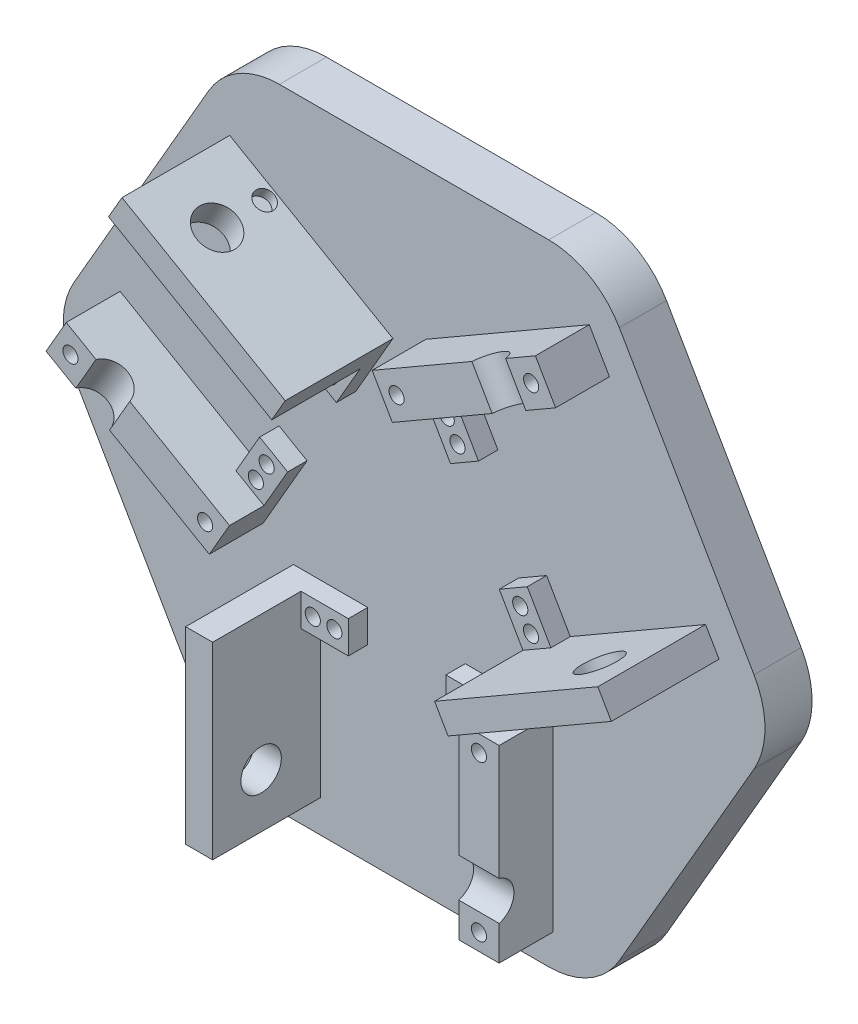
SolidWorks part; units mm, degrees
ref_plane "Front Plane" through (0, 0, 0) normal (0, 0, 1) x (1, 0, 0)
ref_plane "Top Plane" through (0, 0, 0) normal (0, 1, 0) x (1, 0, 0)
ref_plane "Right Plane" through (0, 0, 0) normal (1, 0, 0) x (0, 0, -1)
sketch "Sketch2" plane through (0, 0, 0) normal (0, 0, 1) x (1, 0, 0)
  line L1 (80.1682, 9.6234) -> (48.4182, 64.616)
  line L2 (31.75, 74.2394) -> (-31.75, 74.2394)
  line L3 (-48.4182, 64.616) -> (-80.1682, 9.6234)
  line L4 (-80.1682, -9.6234) -> (-48.4182, -64.616)
  line L5 (-31.75, -74.2394) -> (31.75, -74.2394)
  line L6 (48.4182, -64.616) -> (80.1682, -9.6234)
  circle A0 centre (0, 0) radius 74.2394 construction
  arc A1 (48.4182, 64.616) -> (31.75, 74.2394) centre (31.75, 54.9926) ccw
  arc A2 (80.1682, 9.6234) -> (80.1682, -9.6234) centre (63.5, 0) cw
  arc A3 (31.75, -74.2394) -> (48.4182, -64.616) centre (31.75, -54.9926) ccw
  arc A4 (-48.4182, -64.616) -> (-31.75, -74.2394) centre (-31.75, -54.9926) ccw
  arc A5 (-80.1682, 9.6234) -> (-80.1682, -9.6234) centre (-63.5, 0) ccw
  arc A6 (-31.75, 74.2394) -> (-48.4182, 64.616) centre (-31.75, 54.9926) ccw
  dimension "D1" = 63.5
extrude "Boss-Extrude1" add sketch "Sketch2" along normal blind 4.7625
sketch "Sketch4" plane through (0, 0, 4.7625) normal (0, 0, 1) x (1, 0, 0)
  line L0 (-31.75, -74.2394) -> (31.75, -74.2394) construction
  line L1 (-28.448, -66.6194) -> (-22.098, -66.6194)
  line L2 (-28.448, -66.6194) -> (-28.448, -22.1694)
  line L3 (-28.448, -22.1694) -> (-22.098, -22.1694)
  line L4 (-22.098, -66.6194) -> (-22.098, -22.1694)
  point P6 (0, -74.2394)
  point P17 (0, 0)
  dimension "D1" = 6.35
  dimension "D2" = 44.45
  dimension "D3" = 7.62
  dimension "D4" = 22.098
extrude "Boss-Extrude3" add sketch "Sketch4" along normal blind 25.4
sketch "Sketch5" plane through (0, 0, 4.7625) normal (0, 0, 1) x (1, 0, 0)
  line L1 (23.241, -66.6194) -> (32.766, -66.6194)
  line L2 (23.241, -66.6194) -> (23.241, -22.1694)
  line L3 (23.241, -22.1694) -> (32.766, -22.1694)
  line L4 (32.766, -66.6194) -> (32.766, -22.1694)
  line L6 (-28.448, -66.6194) -> (-22.098, -66.6194) construction
  line L7 (22.733, -61.8823) -> (22.733, -45.9565) construction
  line L8 (-22.098, -22.1694) -> (-28.448, -22.1694) construction
  point P12 (-66.5441, -10.5028)
  point P19 (0, 0)
  dimension "D1" = 9.525
  dimension "D2" = 0.508
extrude "Boss-Extrude6" add sketch "Sketch5" along normal blind 12.7
sketch "Sketch6" plane through (0, 0, 4.7625) normal (0, 0, 1) x (1, 0, 0)
  line L0 (12.065, -22.1694) -> (23.241, -22.1694)
  line L1 (-22.098, -22.1694) -> (-10.922, -22.1694)
  line L2 (-22.098, -22.1694) -> (-22.098, -29.7894)
  line L3 (-22.098, -29.7894) -> (-10.922, -29.7894)
  line L4 (-10.922, -22.1694) -> (-10.922, -29.7894)
  line L5 (12.065, -22.1694) -> (12.065, -29.7894)
  line L6 (12.065, -29.7894) -> (23.241, -29.7894)
  line L7 (23.241, -22.1694) -> (23.241, -29.7894)
  line L8 (23.241, -22.1694) -> (23.241, -66.6194) construction
  line L9 (32.766, -22.1694) -> (23.241, -22.1694) construction
  line L11 (-22.098, -66.6194) -> (-22.098, -22.1694) construction
  point P16 (0, 0)
  dimension "D1" = 7.62
  dimension "D2" = 11.176
  dimension "D3" = 7.62
  dimension "D4" = 11.176
extrude "Boss-Extrude5" add sketch "Sketch6" along normal blind 4.572
sketch "Sketch7" plane through (0, 0, 9.3345) normal (0, 0, 1) x (1, 0, 0)
  line L0 (-22.098, -29.7894) -> (-10.922, -29.7894) construction
  line L1 (-10.922, -29.7894) -> (-10.922, -22.1694) construction
  line L2 (12.065, -29.7894) -> (23.241, -29.7894) construction
  line L3 (12.065, -22.1694) -> (12.065, -29.7894) construction
  circle A0 centre (-19.304, -25.9794) radius 1.7907
  circle A1 centre (-14.224, -25.9794) radius 1.7907
  circle A2 centre (15.367, -25.9794) radius 1.7907
  circle A3 centre (20.447, -25.9794) radius 1.7907
  dimension "D1" = 3.5814
  dimension "D2" = 3.81
  dimension "D8" = 3.5814
  dimension "D9" = 3.5814
  dimension "D10" = 3.5814
  dimension "D3" = 5.08
  dimension "D4" = 3.302
  dimension "D5" = 3.81
  dimension "D6" = 3.302
  dimension "D7" = 5.08
extrude "Cut-Extrude1" cut sketch "Sketch7" against normal blind 6.731
sketch "Sketch9" plane through (-28.448, 0, 0) normal (-1, 0, 0) x (0, 0, 1)
  line L0 (4.7625, -22.1694) -> (4.7625, -66.6194) construction
  line L1 (30.1625, -66.6194) -> (4.7625, -66.6194) construction
  circle A0 centre (7.5311, -53.9194) radius 2.286
  dimension "D1" = 4.572
  dimension "D2" = 2.7686
  dimension "D3" = 12.7
sketch "Sketch10" plane through (-28.448, 0, 0) normal (-1, 0, 0) x (0, 0, 1)
  line L0 (30.1625, -66.6194) -> (4.7625, -66.6194) construction
  circle A0 centre (18.7325, -53.9194) radius 4.7625
  dimension "D1" = 9.525
  dimension "D2" = 11.2014
  dimension "D3" = 12.7
extrude "Cut-Extrude3" cut sketch "Sketch9" against normal blind 2.54
extrude "Cut-Extrude4" cut sketch "Sketch10" against normal up to surface (6.35 mm away) up to face at (-22.098, -39.5261, 14.7532)
sketch3d "3DSketch1"
  line L0 (0, 0, 0) -> (0, 0, 50000) construction
sketch "Sketch11" plane through (23.241, 0, 0) normal (-1, 0, 0) x (0, 0, 1)
  circle A0 centre (18.7325, -53.9194) radius 4.7625 construction
  circle A1 centre (18.7325, -53.9194) radius 4.7625 construction
  circle A2 centre (18.7325, -53.9194) radius 4.7625
  dimension "D1" = 9.525
extrude "Cut-Extrude5" cut sketch "Sketch11" against normal through all
sketch "Sketch12" plane through (0, 0, 17.4625) normal (0, 0, 1) x (1, 0, 0)
  line L0 (32.766, -49.3294) -> (32.766, -22.1694) construction
  line L2 (23.241, -66.6194) -> (32.766, -66.6194) construction
  line L3 (32.766, -22.1694) -> (23.241, -22.1694) construction
  circle A0 centre (28.0035, -26.0683) radius 1.778
  circle A1 centre (28.0035, -62.7205) radius 1.778
  dimension "D1" = 3.556
  dimension "D4" = 3.556
  dimension "D2" = 4.7625
  dimension "D3" = 3.8989
  dimension "D5" = 3.8989
extrude "Cut-Extrude6" cut sketch "Sketch12" against normal blind 6.731
pattern_circular "CirPattern1" count 3 over 360 about axis through (0, 0, 0) along (0, 0, 1) of "Boss-Extrude3", "Boss-Extrude6", "Boss-Extrude5", "Cut-Extrude1", "Cut-Extrude3", "Cut-Extrude4", "Cut-Extrude5", "Cut-Extrude6"
sketch "Sketch14" plane through (0, 0, 0) normal (0, 0, -1) x (-1, 0, 0)
  line L12 (-29.6639, 51.3794) -> (-59.3279, 0)
  line L13 (29.6639, 51.3794) -> (-29.6639, 51.3794)
  line L14 (59.3279, 0) -> (29.6639, 51.3794)
  line L15 (29.6639, -51.3794) -> (59.3279, 0)
  line L16 (-29.6639, -51.3794) -> (29.6639, -51.3794)
  line L17 (-59.3279, 0) -> (-29.6639, -51.3794)
  line L18 (-29.6639, 51.3794) -> (-59.3279, 0)
  line L19 (29.6639, 51.3794) -> (-29.6639, 51.3794)
  line L20 (59.3279, 0) -> (29.6639, 51.3794)
  line L21 (29.6639, -51.3794) -> (59.3279, 0)
  line L22 (-29.6639, -51.3794) -> (29.6639, -51.3794)
  line L23 (-59.3279, 0) -> (-29.6639, -51.3794)
  arc M7 (-31.75, 74.2394) -> (-48.4182, 64.616) centre (-31.75, 54.9926) ccw
  line M8 (-48.4182, 64.616) -> (-80.1682, 9.6234)
  arc M9 (-80.1682, 9.6234) -> (-80.1682, -9.6234) centre (-63.5, 0) ccw
  line M10 (-80.1682, -9.6234) -> (-48.4182, -64.616)
  arc M11 (-48.4182, -64.616) -> (-31.75, -74.2394) centre (-31.75, -54.9926) ccw
  line M12 (-31.75, -74.2394) -> (31.75, -74.2394)
  arc M13 (31.75, -74.2394) -> (48.4182, -64.616) centre (31.75, -54.9926) ccw
  line M14 (48.4182, -64.616) -> (80.1682, -9.6234)
  arc M15 (80.1682, -9.6234) -> (80.1682, 9.6234) centre (63.5, 0) ccw
  line M16 (80.1682, 9.6234) -> (48.4182, 64.616)
  arc M17 (48.4182, 64.616) -> (31.75, 74.2394) centre (31.75, 54.9926) ccw
  line M18 (31.75, 74.2394) -> (-31.75, 74.2394)
  dimension "D1" = 22.86
extrude "Boss-Extrude7" add sketch "Sketch14" along normal blind 6.35 contours L23 L18 L19 L20 L21 L22 M18 M7 M8 M9 M10 M11 M12 M13 M14 M15 M16 M17 region at (0, 72.0161, 0)
